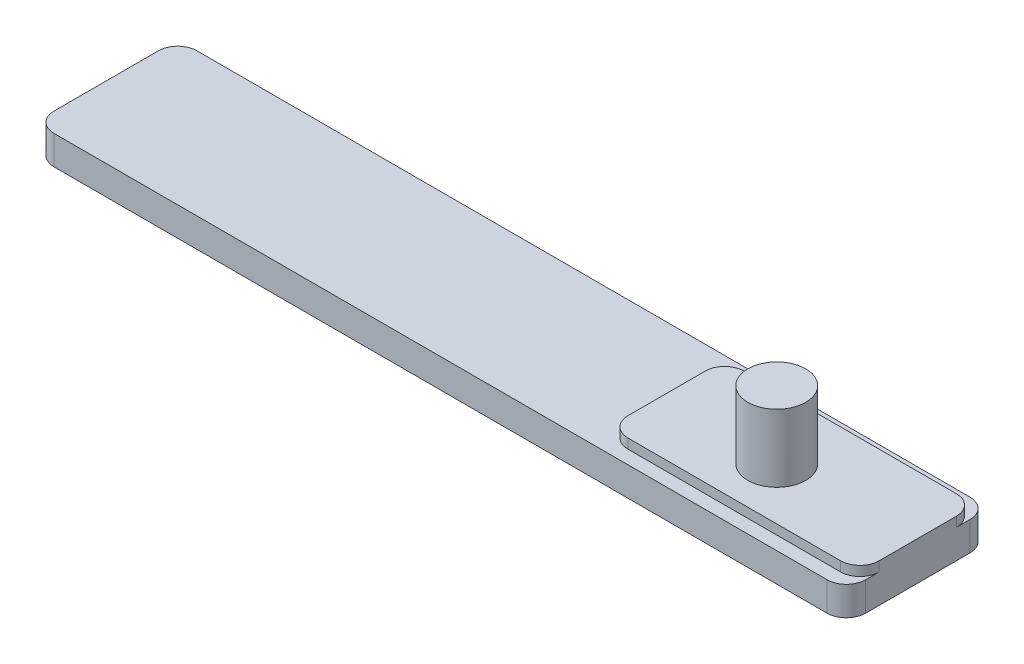
SolidWorks part; units mm, degrees
ref_plane "前视基准面" through (0, 0, 0) normal (0, 0, 1) x (1, 0, 0)
ref_plane "上视基准面" through (0, 0, 0) normal (0, 1, 0) x (1, 0, 0)
ref_plane "右视基准面" through (0, 0, 0) normal (1, 0, 0) x (0, 0, -1)
other "Configuration Table"
sketch "草图1" plane through (0, 0, 0) normal (0, 1, 0) x (1, 0, 0)
  line L1 (0, 0) -> (42, 0)
  line L2 (0, 0) -> (0, 7.4)
  line L3 (0, 7.4) -> (42, 7.4)
  line L4 (42, 0) -> (42, 7.4)
  line L5 (0, 0) -> (42, 7.4) construction
  line L6 (0, 7.4) -> (42, 0) construction
  point P4 (21, 3.7)
  dimension "D1" = 7.4
  dimension "D2" = 42
extrude "凸台-拉伸1" add sketch "草图1" along normal blind 2
sketch "草图2" plane through (0, 2, 0) normal (0, 1, 0) x (1, 0, 0)
  line L0 (0, 0) -> (42, 0) construction
  line L3 (42, 0) -> (42, 7.4) construction
  circle A0 centre (35, 3.4) radius 1.5
  dimension "D1" = 3
  dimension "D2" = 3.4
  dimension "D3" = 7
extrude "凸台-拉伸2" add sketch "草图2" along normal blind 3.5
sketch "草图3" plane through (0, 2, 0) normal (0, 1, 0) x (1, 0, 0)
  line L0 (0, 0) -> (42, 0) construction
  line L1 (0, 7.4) -> (29, 7.4)
  line L2 (0, 7.4) -> (0, 0)
  line L3 (0, 0) -> (29, 0)
  line L4 (29, 7.4) -> (29, 0)
  line L5 (0, 7.4) -> (29, 0) construction
  line L6 (0, 0) -> (29, 7.4) construction
  circle A0 centre (35, 3.4) radius 1.5 construction
  point P4 (14.5, 3.7)
  dimension "D1" = 6
extrude "切除-拉伸1" cut sketch "草图3" against normal blind 0.5
sketch "草图4" plane through (0, 2, 0) normal (0, 1, 0) x (1, 0, 0)
  line L0 (42, 0) -> (42, 7.4) construction
  line L1 (29, 7.4) -> (42, 7.4)
  line L2 (29, 7.4) -> (29, 6.7)
  line L3 (29, 6.7) -> (42, 6.7)
  line L4 (42, 7.4) -> (42, 6.7)
  line L5 (29, 7.4) -> (42, 6.7) construction
  line L6 (29, 6.7) -> (42, 7.4) construction
  line L8 (29, 0) -> (42, 0)
  line L9 (29, 0) -> (29, 0.7)
  line L10 (29, 0.7) -> (42, 0.7)
  line L11 (42, 0) -> (42, 0.7)
  line L12 (29, 0) -> (42, 0.7) construction
  line L13 (29, 0.7) -> (42, 0) construction
  point P4 (35.5, 7.05)
  point P12 (35.5, 0.35)
  dimension "D1" = 0.7
  dimension "D2" = 0.7
extrude "切除-拉伸2" cut sketch "草图4" against normal up to surface (0.5 mm away) up to face at (14.5, 1.5, -3.7)
fillet "圆角1" radius 1 6 edges at (42, 1.75, -0.7) (42, 1.75, -6.7) (0, 0.75, -7.4) (0, 0.75, 0) (29, 1.75, -0.7) (29, 1.75, -6.7)
fillet "圆角2" radius 1 2 edges at (42, 0.75, -7.4) (42, 0.75, 0)
